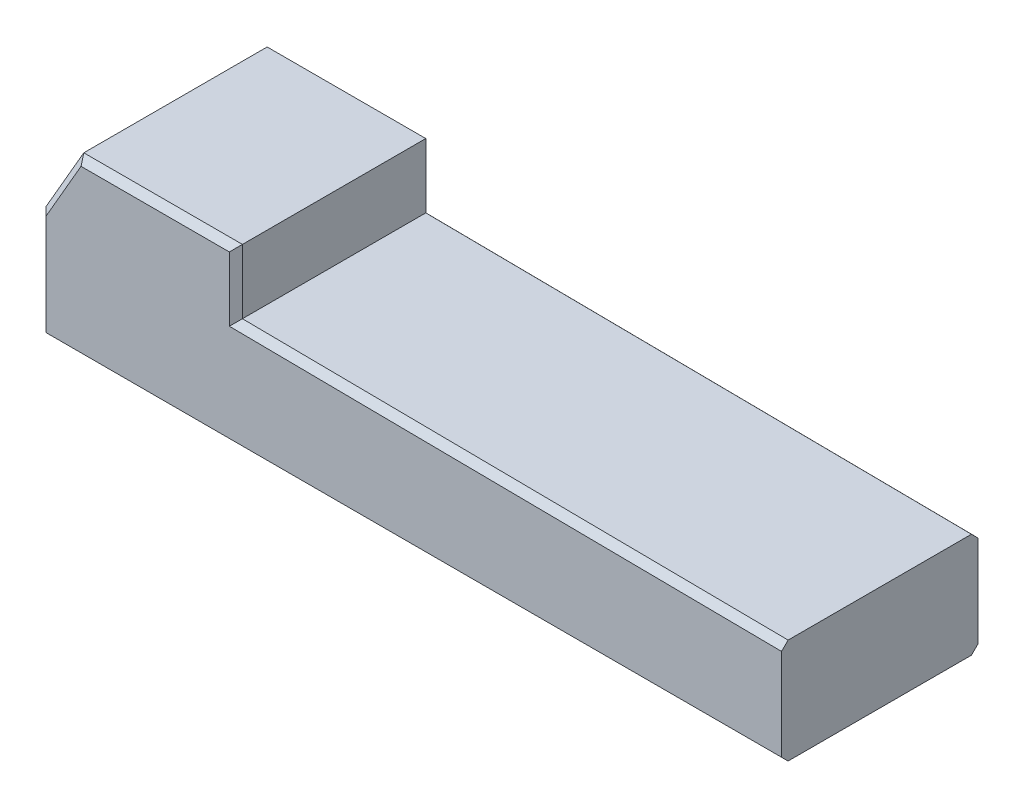
SolidWorks part; units mm, degrees
ref_plane "Front Plane" through (0, 0, 0) normal (0, 0, 1) x (1, 0, 0)
ref_plane "Top Plane" through (0, 0, 0) normal (0, 1, 0) x (1, 0, 0)
ref_plane "Right Plane" through (0, 0, 0) normal (1, 0, 0) x (0, 0, -1)
sketch "BodySke" plane through (0, 0, 0) normal (0, 0, 1) x (1, 0, 0)
  line L0 (0, 0) -> (2000, 0) construction
  line L1 (0, 0) -> (0, 20) construction
  line L2 (0, 20) -> (2000, 0) construction
  line L3 (80, 19.2) -> (80, 0)
  line L4 (80, 0) -> (0, 0)
  line L5 (0, 20) -> (80, 19.2)
  line L6 (0, 0) -> (-20, 0)
  line L7 (-20, 0) -> (-20, 20.2) construction
  line L8 (-20, 20.2) -> (0, 20)
  line L9 (-20, 20.2) -> (-20, 32)
  line L10 (-20, 32) -> (-56, 32) construction
  line L11 (-56, 32) -> (-56, 0) construction
  line L12 (-56, 0) -> (-20, 0)
  line L13 (-56, 20) -> (-49.0718, 32)
  line L14 (-49.0718, 32) -> (-20, 32)
  line L15 (-56, 20) -> (-56, 0)
  dimension "D2" = 2000
  dimension "Length" = 100
  dimension "D3" = 20
  dimension "Width" = 36
extrude "BaseBody" add sketch "BodySke" along normal blind 36
chamfer "Chamfer1" distance 1.2 angle 45 12 edges at (30, 19.7, 0) (12, 0, 0) (12, 0, 36) (30, 19.7, 36) (-34.5359, 32, 0) (-52.5359, 26, 0) (-56, 10, 0) (-56, 10, 36) (-52.5359, 26, 36) (-34.5359, 32, 36) (-20, 26.1, 36) (-20, 26.1, 0)
equation "\"D2@BodySke\" = \"Height@BodySke\" * 100"
equation "\"D3@BodySke\" = \"Height@BodySke\""
equation "\"Width@BaseBody\" = \"Width@BodySke\""
